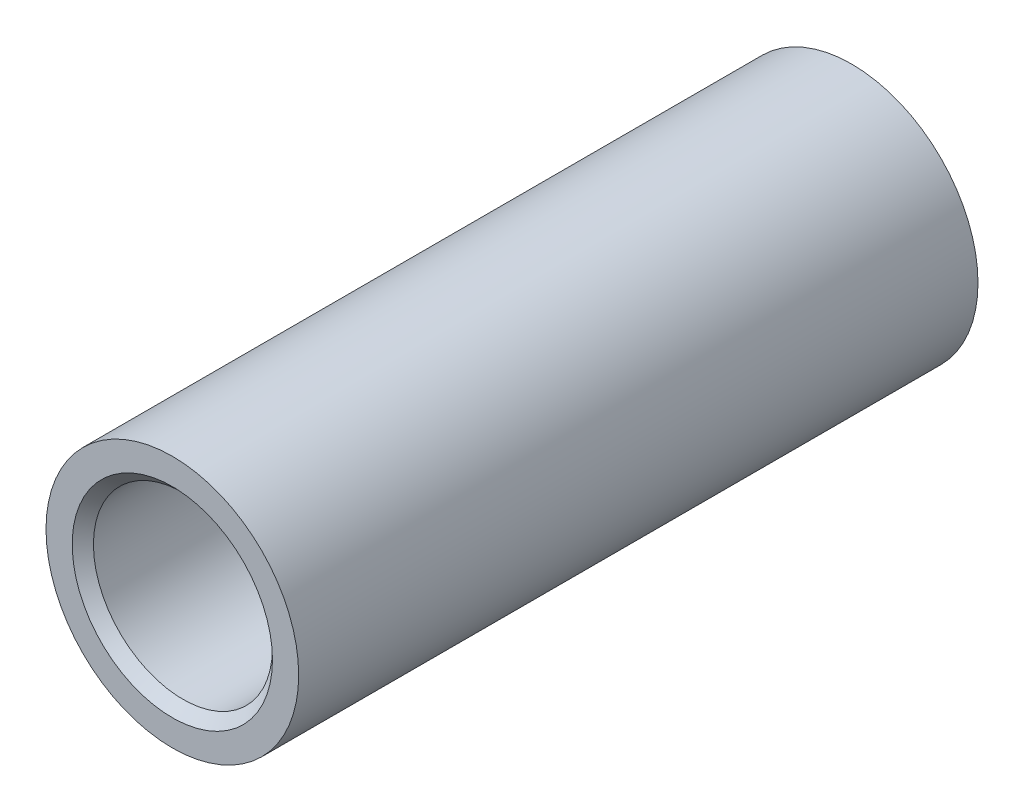
SolidWorks part; units mm, degrees
ref_plane "Front Plane" through (0, 0, 0) normal (0, 0, 1) x (1, 0, 0)
ref_plane "Top Plane" through (0, 0, 0) normal (0, 1, 0) x (1, 0, 0)
ref_plane "Right Plane" through (0, 0, 0) normal (1, 0, 0) x (0, 0, -1)
sketch "Sketch1" plane through (0, 0, 0) normal (0, 0, 1) x (1, 0, 0)
  circle A0 centre (0, 0) radius 3.375
  circle A1 centre (0, 0) radius 4.7625
  dimension "D1" = 6.75
  dimension "D2" = 9.525
extrude "Boss-Extrude1" add sketch "Sketch1" along normal blind 25.608
chamfer "Chamfer1" distance 0.4 angle 45 2 edges at (3.375, 0, 0) (3.375, 0, 25.608)
